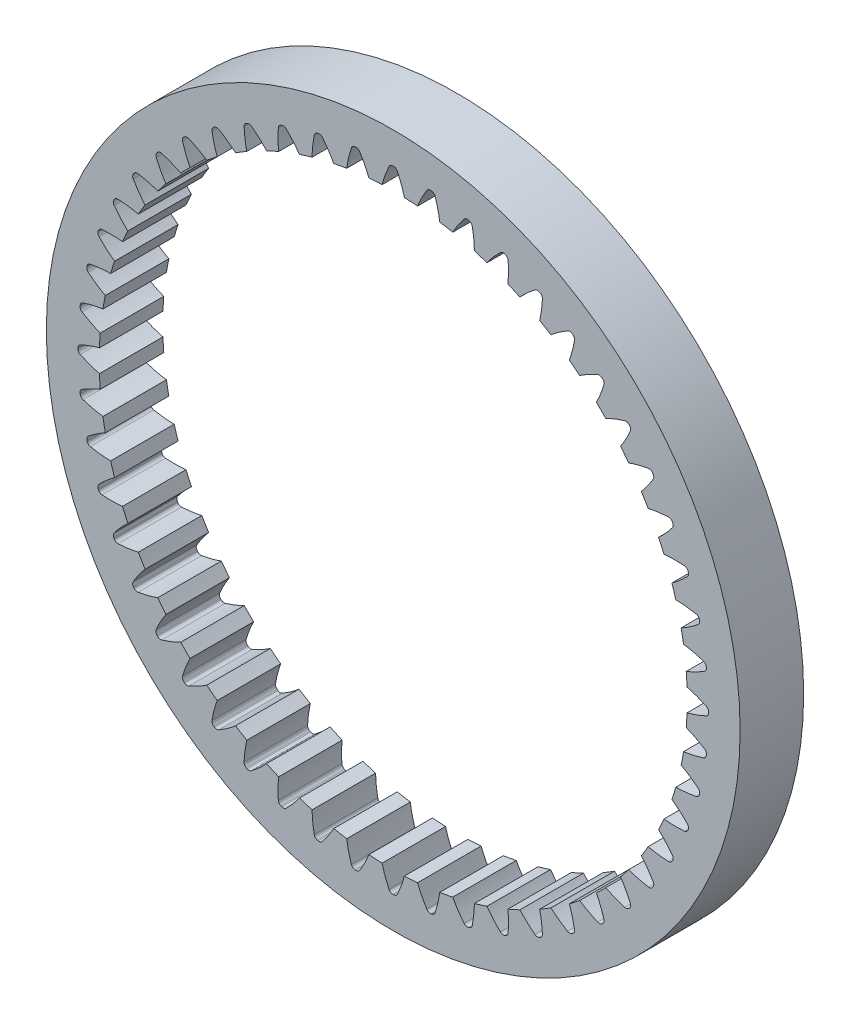
SolidWorks part; units mm, degrees
ref_plane "Front Plane" through (0, 0, 0) normal (0, 0, 1) x (1, 0, 0)
ref_plane "Top Plane" through (0, 0, 0) normal (0, 1, 0) x (1, 0, 0)
ref_plane "Right Plane" through (0, 0, 0) normal (1, 0, 0) x (0, 0, -1)
ref_axis "Axis1" through (0, 0, 2.8875) along (0, 0, -1)
sketch "Sketch3" plane through (0, 0, 0) normal (0, 0, 1) x (1, 0, 0)
  circle A0 centre (0, 0) radius 15.015
  circle A1 centre (0, 0) radius 12.725
  dimension "D1" = 30.03
  dimension "D2" = 25.45
extrude "Boss-Extrude2" add sketch "Sketch3" along normal blind 2.75
sketch "Sketch1" plane through (0, 0, 0) normal (0, 0, 1) x (1, 0, 0)
  line L8 (13.5488, 0.1808) -> (13.5488, -0.1808) construction
  line L10 (12.7158, 0.4827) -> (12.7158, -0.4827)
  line L11 (13.65, 0.0227) -> (13.65, -0.0227)
  circle A0 centre (0, 0) radius 12.725 construction
  circle A4 centre (0, 0) radius 13.65 construction
  arc A5 (13.5488, 0.1808) -> (13.65, 0.0227) centre (13.4753, 0.0224) cw
  arc A6 (13.5488, -0.1808) -> (13.65, -0.0227) centre (13.4753, -0.0224) ccw
  spline S0 degree 4 poles (12.6523, 0.498) (12.6569, 0.4969) (12.6657, 0.4949) (12.6776, 0.4921) (12.7085, 0.4845) (12.7233, 0.4808) (12.761, 0.4711) (12.7837, 0.465) (12.8146, 0.4565) (12.8404, 0.4491) (12.8693, 0.4407) (12.8962, 0.4326) (12.9242, 0.4241) (12.9514, 0.4155) (12.9791, 0.4066) (13.0063, 0.3976) (13.0338, 0.3884) (13.0661, 0.3773) (13.1057, 0.3633) (13.1509, 0.347) (13.2043, 0.3268) (13.2565, 0.3066) (13.3125, 0.284) (13.3618, 0.2638) (13.4214, 0.238) (13.4633, 0.2199) (13.5299, 0.1896) (13.5582, 0.1765) (13.601, 0.1564) (13.619, 0.1477) (13.6288, 0.143) knots 0 0 0 0 0 0.015716 0.031433 0.062363 0.090067 0.117772 0.145476 0.173181 0.200885 0.22859 0.256294 0.283999 0.311703 0.339408 0.367112 0.394817 0.422521 0.471488 0.526897 0.582306 0.637715 0.693124 0.748533 0.803942 0.859351 0.91476 0.95738 1 1 1 1 1 construction
  spline S1 degree 4 poles (12.7158, 0.4827) (12.7218, 0.4812) (12.7335, 0.4782) (12.761, 0.4711) (12.7837, 0.465) (12.8146, 0.4565) (12.8404, 0.4491) (12.8693, 0.4407) (12.8962, 0.4326) (12.9242, 0.4241) (12.9514, 0.4155) (12.9791, 0.4066) (13.0063, 0.3976) (13.0338, 0.3884) (13.0661, 0.3773) (13.1057, 0.3633) (13.1509, 0.347) (13.2043, 0.3268) (13.2565, 0.3066) (13.3125, 0.284) (13.3618, 0.2638) (13.4214, 0.238) (13.4633, 0.2199) (13.5163, 0.1958) (13.5376, 0.186) (13.5488, 0.1808) knots 0.062363 0.062363 0.062363 0.062363 0.062363 0.090067 0.117772 0.145476 0.173181 0.200885 0.22859 0.256294 0.283999 0.311703 0.339408 0.367112 0.394817 0.422521 0.471488 0.526897 0.582306 0.637715 0.693124 0.748533 0.803942 0.859351 0.91476 0.91476 0.91476 0.91476 0.91476
  spline S2 degree 4 poles (12.6523, -0.498) (12.6569, -0.4969) (12.6657, -0.4949) (12.6776, -0.4921) (12.7085, -0.4845) (12.7233, -0.4808) (12.761, -0.4711) (12.7837, -0.465) (12.8146, -0.4565) (12.8404, -0.4491) (12.8693, -0.4407) (12.8962, -0.4326) (12.9242, -0.4241) (12.9514, -0.4155) (12.9791, -0.4066) (13.0063, -0.3976) (13.0338, -0.3884) (13.0661, -0.3773) (13.1057, -0.3633) (13.1509, -0.347) (13.2043, -0.3268) (13.2565, -0.3066) (13.3125, -0.284) (13.3618, -0.2638) (13.4214, -0.238) (13.4633, -0.2199) (13.5299, -0.1896) (13.5582, -0.1765) (13.601, -0.1564) (13.619, -0.1477) (13.6288, -0.143) knots 0 0 0 0 0 0.015716 0.031433 0.062363 0.090067 0.117772 0.145476 0.173181 0.200885 0.22859 0.256294 0.283999 0.311703 0.339408 0.367112 0.394817 0.422521 0.471488 0.526897 0.582306 0.637715 0.693124 0.748533 0.803942 0.859351 0.91476 0.95738 1 1 1 1 1 construction
  spline S3 degree 4 poles (12.7158, -0.4827) (12.7218, -0.4812) (12.7335, -0.4782) (12.761, -0.4711) (12.7837, -0.465) (12.8146, -0.4565) (12.8404, -0.4491) (12.8693, -0.4407) (12.8962, -0.4326) (12.9242, -0.4241) (12.9514, -0.4155) (12.9791, -0.4066) (13.0063, -0.3976) (13.0338, -0.3884) (13.0661, -0.3773) (13.1057, -0.3633) (13.1509, -0.347) (13.2043, -0.3268) (13.2565, -0.3066) (13.3125, -0.284) (13.3618, -0.2638) (13.4214, -0.238) (13.4633, -0.2199) (13.5163, -0.1958) (13.5376, -0.186) (13.5488, -0.1808) knots 0.062363 0.062363 0.062363 0.062363 0.062363 0.090067 0.117772 0.145476 0.173181 0.200885 0.22859 0.256294 0.283999 0.311703 0.339408 0.367112 0.394817 0.422521 0.471488 0.526897 0.582306 0.637715 0.693124 0.748533 0.803942 0.859351 0.91476 0.91476 0.91476 0.91476 0.91476
  dimension "D1" = 25.45
  dimension "D3" = 27.3
extrude "Cut-Extrude2" cut sketch "Sketch1" along normal through all
pattern_circular "CirPattern1" count 52 over 360 about axis through (0, 0, 2.8875) along (0, 0, -1) of "Cut-Extrude2"
sketch "Sketch4" plane through (0, 0, 2.75) normal (0, 0, 1) x (1, 0, 0)
  circle A0 centre (0, 0) radius 17
  circle A1 centre (0, 0) radius 15.015
  circle A2 centre (0, 0) radius 15.015 construction
  dimension "D1" = 34
extrude "width-match" [suppressed] add sketch "Sketch4" against normal up to surface (2.75 mm away) up to face at (0, 0, 0)
sketch "Sketch5" plane through (0, 0, 0) normal (0, 0, 1) x (1, 0, 0)
  line L0 (1.8709, 0) -> (-9.8171, 0) construction
  line L1 (18.2, 1.2) -> (18.2, 0) construction
  circle A0 centre (17, 0) radius 1 construction
  arc A1 (18.2, 2.2) -> (18.2, -2.2) centre (18.2, 0) ccw
  arc A2 (18.2, 0.2) -> (18.2, -0.2) centre (18.2, 0) ccw
  arc A4 (18.2, 2.2) -> (18.2, 0.2) centre (18.2, 1.2) cw
  arc A5 (18.2, -2.2) -> (18.2, -0.2) centre (18.2, -1.2) ccw
  dimension "D1" = 2.2
  dimension "D2" = 1
  dimension "D3" = 17
extrude "Cut-Extrude3" [suppressed] cut sketch "Sketch5" against normal through all both and the other way through all
pattern_circular "CirPattern2" [suppressed] count 4 over 360 about axis through (0, 0, 2.8875) along (0, 0, -1) of bodies 132
equation "\"S1_Module\"= 0.5\t\t'tooth per mm"
equation "\"R1_NumTeeth\"= 52"
equation "\"P1_teeth\"= 10"
equation "\"R2_teeth\"= 51"
equation "\"S1_PressureAngle\"= 20'deg. leave unitless"
equation "\"sun_teeth\"= \"R1_NumTeeth\" - 2 * \"P1_teeth\""
equation "\"S2_Module\"= 0.5121951219512195\t\t\t'stage two gear modules CAN be different from stage 1; this makes things a lot more complicated though so try and avoid it if you can"
equation "\"S2_PressureAngle\"= \"S1_PressureAngle\"'stage two pressure angle can be different, but for simplicity keep it the same"
equation "\"S1_carrier_radius\"= \"P1_teeth\" * \"S1_Module\" / 2  + \"sun_teeth\" * \"S1_Module\" / 2"
equation "\"P2_teeth\" = 10"
equation "\"Ring_profile_shift\" = 0.05"
equation "\"Planet_profile_shift\" = -0.05"
equation "\"Planet_broachcutter_offset\" = -0.0"
equation "\"Ring_broachcutter_offset\" = 0.0"
equation "\"Nteeth\"= \"R1_NumTeeth\""
equation "\"module\"= \"S1_Module\""
equation "\"pressure_angle\"= \"S1_PressureAngle\" * pi / 180"
equation "\"x_shift\"= \"Ring_profile_shift\""
equation "\"r_p\"= \"module\" * \"Nteeth\" / 2'pitch circle radius"
equation "\"r_b\"= \"r_p\" * cos ( \"pressure_angle\" )'base circle radius"
equation "\"r_f\"= \"r_p\" + \"module\" * ( 1.25 + \"x_shift\" )"
equation "\"head\"= - 0.4 'Default. A clearance parameter applied to the addendum in internal gears. Removes material for clearance"
equation "\"r_a\"= \"r_p\" - \"module\" * ( 1 - \"x_shift\" + \"head\" ) 'addendum"
equation "\"ttoaddendum\"= sqr ( ( \"r_a\" / \"r_b\" ) * ( \"r_a\" / \"r_b\" ) - 1 )"
equation "\"tmax\"= sqr ( ( ( \"r_f\" - 0.1 ) / \"r_b\" ) ^ 2 - 1 )"
equation "\"toothoffset\"= pi / \"Nteeth\"'Kludge. If odd number of teeth, remove the *0. If even, add a *0. Its to clock the midplane to the void between teeth for alignment in planetary stacks"
equation "\"t_p\"= sqr ( ( \"r_p\" / \"r_b\" ) ^ 2 - 1 )'t at pitch circle"
equation "\"x_p\"= \"r_b\" * ( cos ( \"t_p\" ) + \"t_p\" * sin ( \"t_p\" ) )"
equation "\"y_p\"= \"r_b\" * ( sin ( \"t_p\" ) - \"t_p\" * cos ( \"t_p\" ) )"
equation "\"theta_p\"= atn ( \"y_p\" / \"x_p\" )"
equation "\"des_ang\"= ( pi / 2 - 2 * \"x_shift\" * tan ( \"pressure_angle\" ) ) / \"Nteeth\""
equation "\"delta\"= \"des_ang\" - \"theta_p\""
equation "\"delta2\"= \"delta\" + 2 * pi * ( \"Nteeth\" - 1 ) / \"Nteeth\""
equation "\"height\"=2.75"
equation "\"involute_offset\"= \"Ring_broachcutter_offset\"'Hit CTL+q after changing this or it wont update properly"
equation "\"D1@Sketch1\"=\"r_a\"*2"
equation "\"D1@Sketch3\"=\"r_f\"*2.2"
equation "\"D2@Sketch3\"=(\"r_a\"+\"involute_offset\")*2"
equation "\"D3@Sketch1\"=\"r_f\"*2"
equation "\"D1@CirPattern1\"=\"Nteeth\""
equation "\"D1@Boss-Extrude2\"=\"height\""
